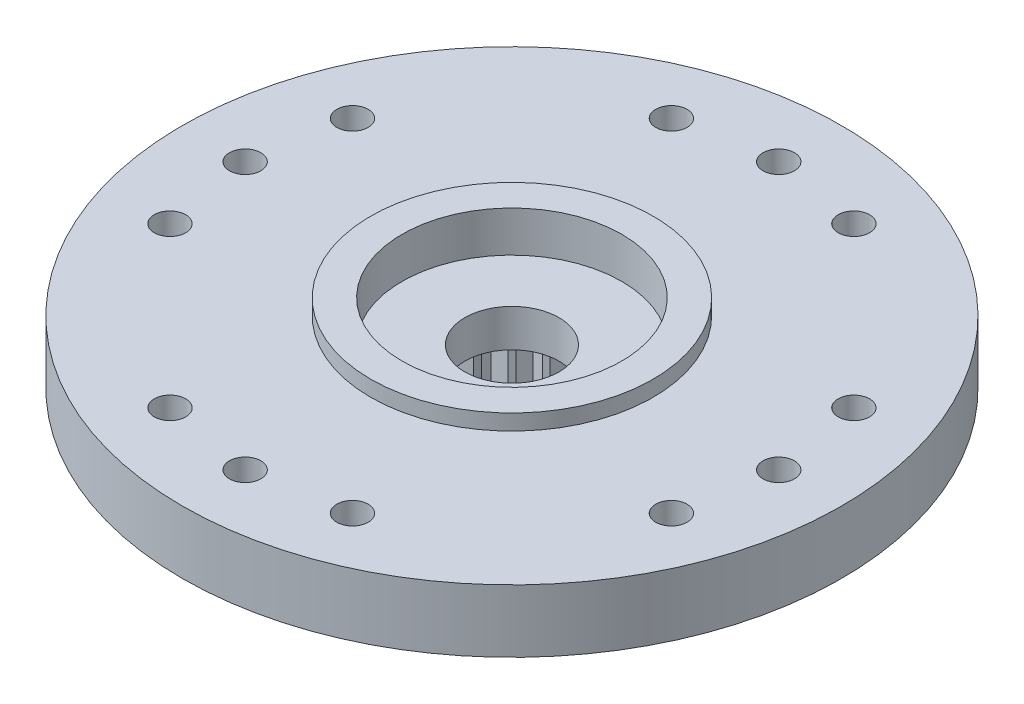
SolidWorks part; units mm, degrees
ref_plane "Front Plane" through (0, 0, 0) normal (0, 0, 1) x (1, 0, 0)
ref_plane "Top Plane" through (0, 0, 0) normal (0, 1, 0) x (1, 0, 0)
ref_plane "Right Plane" through (0, 0, 0) normal (1, 0, 0) x (0, 0, -1)
sketch "Sketch1" plane through (0, 0, 0) normal (0, 1, 0) x (1, 0, 0)
  line L0 (0, 10.5) -> (0, -10.5) construction
  line L1 (-10.5, 0) -> (10.5, 0) construction
  line L2 (0, 0) -> (3.4202, 9.3969) construction
  line L3 (-3.4202, 9.3969) -> (0, 0) construction
  line L4 (0, 0) -> (7.9874, 2.9072) construction
  line L5 (0, 0) -> (7.9874, -2.9072) construction
  circle A0 centre (0, 0) radius 10.5
  circle A1 centre (0, 0) radius 1.5
  circle A2 centre (0, 0) radius 7 construction
  circle A3 centre (0, 0) radius 10 construction
  circle A4 centre (0, 0) radius 8.5 construction
  circle A5 centre (2.9072, 7.9874) radius 0.5
  circle A6 centre (-2.9072, 7.9874) radius 0.5
  circle A7 centre (2.9072, -7.9874) radius 0.5
  circle A8 centre (-2.9072, -7.9874) radius 0.5
  circle A9 centre (0, -8.5) radius 0.5
  circle A11 centre (8.5, 0) radius 0.5
  circle A12 centre (7.9874, 2.9072) radius 0.5
  circle A13 centre (7.9874, -2.9072) radius 0.5
  circle A20 centre (-7.9874, -2.9072) radius 0.5
  circle A21 centre (-8.5, 0) radius 0.5
  circle A22 centre (-7.9874, 2.9072) radius 0.5
  circle A23 centre (0, 8.5) radius 0.5
  dimension "D1" = 21
  dimension "D2" = 3
  dimension "D3" = 14
  dimension "D4" = 20
  dimension "D5" = 17
  dimension "D6" = 1
  dimension "D7" = 1
  dimension "D16" = 1
  dimension "D17" = 1
  dimension "D18" = 1
  dimension "D19" = 1
  dimension "D8" = 20
  dimension "D10" = 20
  dimension "D14" = 20
  dimension "D15" = 20
extrude "Boss-Extrude1" add sketch "Sketch1" along normal blind 2
sketch "Sketch2" plane through (0, 2, 0) normal (0, 1, 0) x (1, 0, 0)
  circle A0 centre (0, 0) radius 4.5
  circle A1 centre (0, 0) radius 3.5
  dimension "D1" = 9
  dimension "D2" = 1
extrude "Boss-Extrude2" add sketch "Sketch2" along normal blind 0.5
sketch "Sketch3" plane through (0, 2, 0) normal (0, 1, 0) x (1, 0, 0)
  circle A0 centre (0, 0) radius 1.5 construction
  circle A1 centre (0, 0) radius 3.5 construction
  circle A2 centre (0, 0) radius 1.5
  circle A3 centre (0, 0) radius 3.5
extrude "Cut-Extrude1" cut sketch "Sketch3" against normal blind 0.8
sketch "Sketch4" plane through (0, 0, 0) normal (0, -1, 0) x (1, 0, 0)
  circle A0 centre (0, 0) radius 4.5
  circle A1 centre (0, 0) radius 2.5
  dimension "D1" = 9
  dimension "D2" = 2
extrude "Boss-Extrude3" add sketch "Sketch4" along normal blind 2.5
sketch "Sketch5" plane through (0, -2.5, 0) normal (0, -1, 0) x (1, 0, 0)
  line L0 (0, 0) -> (0, 0.6245) construction
  line L1 (0, 3) -> (-0.299, 2.4821)
  line L2 (0, 3) -> (0.299, 2.4821)
  line L3 (0.9271, 2.8532) -> (0.4826, 2.453)
  line L4 (0.9271, 2.8532) -> (1.0514, 2.2682)
  line L5 (1.7634, 2.4271) -> (1.217, 2.1838)
  line L6 (1.7634, 2.4271) -> (1.7008, 1.8323)
  line L7 (2.4271, 1.7634) -> (1.8323, 1.7008)
  line L8 (2.4271, 1.7634) -> (2.1838, 1.217)
  line L9 (2.8532, 0.9271) -> (2.2682, 1.0514)
  line L10 (2.8532, 0.9271) -> (2.453, 0.4826)
  line L11 (3, 0) -> (2.4821, 0.299)
  line L12 (3, 0) -> (2.4821, -0.299)
  line L13 (2.8532, -0.9271) -> (2.453, -0.4826)
  line L14 (2.8532, -0.9271) -> (2.2682, -1.0514)
  line L15 (2.4271, -1.7634) -> (2.1838, -1.217)
  line L16 (2.4271, -1.7634) -> (1.8323, -1.7008)
  line L17 (1.7634, -2.4271) -> (1.7008, -1.8323)
  line L18 (1.7634, -2.4271) -> (1.217, -2.1838)
  line L19 (0.9271, -2.8532) -> (1.0514, -2.2682)
  line L20 (0.9271, -2.8532) -> (0.4826, -2.453)
  line L21 (0, -3) -> (0.299, -2.4821)
  line L22 (0, -3) -> (-0.299, -2.4821)
  line L23 (-0.9271, -2.8532) -> (-0.4826, -2.453)
  line L24 (-0.9271, -2.8532) -> (-1.0514, -2.2682)
  line L25 (-1.7634, -2.4271) -> (-1.217, -2.1838)
  line L26 (-1.7634, -2.4271) -> (-1.7008, -1.8323)
  line L27 (-2.4271, -1.7634) -> (-1.8323, -1.7008)
  line L28 (-2.4271, -1.7634) -> (-2.1838, -1.217)
  line L29 (-2.8532, -0.9271) -> (-2.2682, -1.0514)
  line L30 (-2.8532, -0.9271) -> (-2.453, -0.4826)
  line L31 (-3, 0) -> (-2.4821, -0.299)
  line L32 (-3, 0) -> (-2.4821, 0.299)
  line L33 (-2.8532, 0.9271) -> (-2.453, 0.4826)
  line L34 (-2.8532, 0.9271) -> (-2.2682, 1.0514)
  line L35 (-2.4271, 1.7634) -> (-2.1838, 1.217)
  line L36 (-2.4271, 1.7634) -> (-1.8323, 1.7008)
  line L37 (-1.7634, 2.4271) -> (-1.7008, 1.8323)
  line L38 (-1.7634, 2.4271) -> (-1.217, 2.1838)
  line L39 (-0.9271, 2.8532) -> (-1.0514, 2.2682)
  line L40 (-0.9271, 2.8532) -> (-0.4826, 2.453)
  circle A0 centre (0, 0) radius 2.5 construction
  arc A1 (-2.1838, 1.217) -> (-2.2682, 1.0514) centre (0, 0) ccw
  arc A2 (-1.7008, 1.8323) -> (-1.8323, 1.7008) centre (0, 0) ccw
  arc A3 (-1.0514, 2.2682) -> (-1.217, 2.1838) centre (0, 0) ccw
  arc A4 (-0.299, 2.4821) -> (-0.4826, 2.453) centre (0, 0) ccw
  arc A5 (0.4826, 2.453) -> (0.299, 2.4821) centre (0, 0) ccw
  arc A6 (1.217, 2.1838) -> (1.0514, 2.2682) centre (0, 0) ccw
  arc A7 (1.8323, 1.7008) -> (1.7008, 1.8323) centre (0, 0) ccw
  arc A8 (2.2682, 1.0514) -> (2.1838, 1.217) centre (0, 0) ccw
  arc A9 (2.4821, 0.299) -> (2.453, 0.4826) centre (0, 0) ccw
  arc A10 (2.453, -0.4826) -> (2.4821, -0.299) centre (0, 0) ccw
  arc A11 (2.1838, -1.217) -> (2.2682, -1.0514) centre (0, 0) ccw
  arc A12 (1.7008, -1.8323) -> (1.8323, -1.7008) centre (0, 0) ccw
  arc A13 (1.0514, -2.2682) -> (1.217, -2.1838) centre (0, 0) ccw
  arc A14 (0.299, -2.4821) -> (0.4826, -2.453) centre (0, 0) ccw
  arc A15 (-0.4826, -2.453) -> (0, -2.5) centre (0, 0) ccw
  arc A16 (-1.217, -2.1838) -> (-1.0514, -2.2682) centre (0, 0) ccw
  arc A17 (-1.8323, -1.7008) -> (-1.7008, -1.8323) centre (0, 0) ccw
  arc A18 (-2.2682, -1.0514) -> (-2.1838, -1.217) centre (0, 0) ccw
  arc A19 (-2.4821, -0.299) -> (-2.453, -0.4826) centre (0, 0) ccw
  arc A20 (-2.453, 0.4826) -> (-2.4821, 0.299) centre (0, 0) ccw
  point P68 (0, 0)
  circle M5 centre (0, 0) radius 2.5
  dimension "D1" = 30
  dimension "D2" = 3
  dimension "D3" = 20
extrude "Cut-Extrude3" cut sketch "Sketch5" against normal up to surface (2.5 mm away) contours L36 L35 M5 | L34 L33 M5 | L32 L31 M5 | L30 L29 M5 | L28 L27 M5 | L26 L25 M5 | L24 L23 M5 | L0 L21 M5 | L22 L0 M5 | L20 L19 M5 | L18 L17 M5 | L16 L15 M5 | L14 L13 M5 | L12 L11 M5 | L10 L9 M5 | L8 L7 M5 | L6 L5 M5 | L4 L3 M5 | L0 L2 M5 | L0 L1 M5 | L40 L39 M5 | L38 L37 M5 region at (0, -2.5, 2.6627) region at (-0.8228, -2.5, 2.5324) region at (0.8228, -2.5, 2.5324) region at (-1.5651, -2.5, 2.1542) region at (1.5651, -2.5, 2.1542) region at (-2.1542, -2.5, 1.5651) region at (2.1542, -2.5, 1.5651) region at (-2.5324, -2.5, 0.8228) region at (2.5324, -2.5, 0.8228) region at (-2.6627, -2.5, 0) region at (2.6627, -2.5, 0) region at (-2.5324, -2.5, -0.8228) region at (2.5324, -2.5, -0.8228) region at (-2.1542, -2.5, -1.5651) region at (2.1542, -2.5, -1.5651) region at (-1.5651, -2.5, -2.1542) region at (1.5651, -2.5, -2.1542) region at (-0.8228, -2.5, -2.5324) region at (0.8228, -2.5, -2.5324) region at (0, -2.5, -2.6627) up to face at (0, 0, 1.5)
